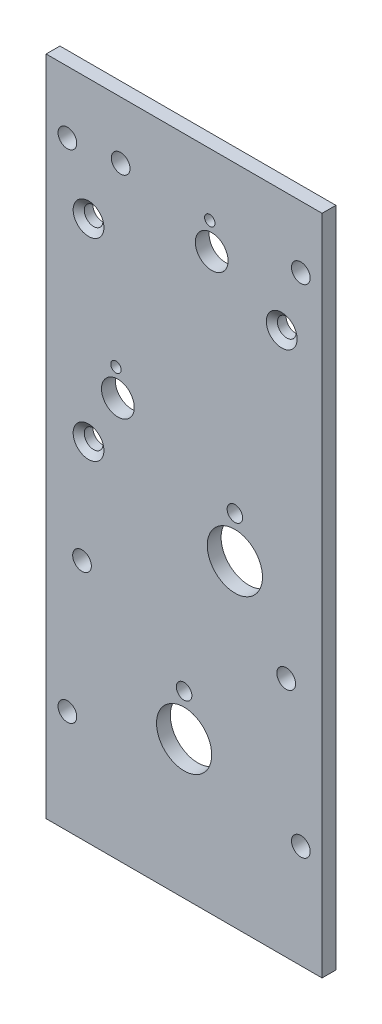
SolidWorks part; units mm, degrees
material "Acrylic (Medium-high impact)"
ref_plane "Front Plane" through (0, 0, 0) normal (0, 0, 1) x (1, 0, 0)
ref_plane "Top Plane" through (0, 0, 0) normal (0, 1, 0) x (1, 0, 0)
ref_plane "Right Plane" through (0, 0, 0) normal (1, 0, 0) x (0, 0, -1)
sketch "Sketch1" plane through (0, 0, 0) normal (0, 0, 1) x (1, 0, 0)
  line L8 (31.75, -152.4) -> (31.75, 0)
  line L9 (31.75, 0) -> (-31.75, 0)
  line L10 (-31.75, 0) -> (-31.75, -152.4)
  line L11 (-31.75, -152.4) -> (31.75, -152.4)
extrude "Boss-Extrude1" add sketch "Sketch1" against normal blind 3.175
hole_wizard "#6 Clearance Hole1" positions "Sketch3" profile "Sketch2" hole size "#6" standard "ANSI Inch" end condition up to next
sketch "Sketch3" plane through (0, 0, 0) normal (0, 0, 1) x (1, 0, 0)
  point P0 (-26.8605, -14.2875)
  point P2 (26.8605, -14.2875)
  point P4 (26.8605, -128.5875)
  point P6 (-26.8605, -128.5875)
sketch "Sketch2" plane through (-26.8605, -14.2875, 0) normal (1, 0, 0) x (0, -1, 0)
  line L0 (0, 0) -> (0, 3.175)
  line L1 (0, 3.175) -> (2.1526, 3.175)
  line L2 (2.1526, 3.175) -> (2.1526, 0)
  line L5 (2.1526, 0) -> (0, 0)
  line L11 (0, -6.35) -> (0, 107.95) construction
  dimension "Thru Hole Dia." = 4.3053
  dimension "Thru Hole Depth" = 3.175
hole_wizard "#6 Clearance Hole2" positions "Sketch5" profile "Sketch4" hole size "#6" standard "ANSI Inch" end condition up to next
sketch "Sketch5" plane through (0, 0, 0) normal (0, 0, 1) x (1, 0, 0)
  point P0 (-23.495, -96.8375)
  point P2 (23.495, -96.8375)
  point P4 (-14.605, -13.208)
sketch "Sketch4" plane through (-23.495, -96.8375, 0) normal (1, 0, 0) x (0, -1, 0)
  line L0 (0, 0) -> (0, 3.175)
  line L1 (0, 3.175) -> (2.1526, 3.175)
  line L2 (2.1526, 3.175) -> (2.1526, 0)
  line L5 (2.1526, 0) -> (0, 0)
  line L11 (0, -6.35) -> (0, 107.95) construction
  dimension "Thru Hole Dia." = 4.3053
  dimension "Thru Hole Depth" = 3.175
hole_wizard "1/2 (0.5) Diameter Hole1" positions "Sketch7" profile "Sketch6" hole size "1/2" standard "ANSI Inch" end condition up to next
sketch "Sketch7" plane through (0, 0, 0) normal (0, 0, 1) x (1, 0, 0)
  point P4 (11.684, -79.375)
  point P6 (0, -120.65)
sketch "Sketch6" plane through (11.684, -79.375, 0) normal (1, 0, 0) x (0, -1, 0)
  line L0 (0, 0) -> (0, 3.175)
  line L1 (0, 3.175) -> (6.35, 3.175)
  line L2 (6.35, 3.175) -> (6.35, 0)
  line L5 (6.35, 0) -> (0, 0)
  line L11 (0, -6.35) -> (0, 107.95) construction
  dimension "Thru Hole Dia." = 12.7
  dimension "Thru Hole Depth" = 3.175
hole_wizard "9/64 (0.14063) Diameter Hole1" positions "Sketch9" profile "Sketch8" hole size "9/64" standard "ANSI Inch" end condition up to next
sketch "Sketch9" plane through (0, 0, 0) normal (0, 0, 1) x (1, 0, 0)
  point P0 (0, -111.125)
  point P2 (11.684, -69.85)
sketch "Sketch8" plane through (0, -111.125, 0) normal (1, 0, 0) x (0, -1, 0)
  line L0 (0, 0) -> (0, 3.175)
  line L1 (0, 3.175) -> (1.786, 3.175)
  line L2 (1.786, 3.175) -> (1.786, 0)
  line L5 (1.786, 0) -> (0, 0)
  line L11 (0, -6.35) -> (0, 107.95) construction
  dimension "Thru Hole Dia." = 3.572
  dimension "Thru Hole Depth" = 3.175
hole_wizard "19/64 (0.29688) Diameter Hole1" positions "Sketch11" profile "Sketch10" hole size "19/64" standard "ANSI Inch" end condition up to next
sketch "Sketch11" plane through (0, 0, 0) normal (0, 0, 1) x (1, 0, 0)
  point P0 (-15.24, -60.325)
  point P2 (6.35, -20.32)
sketch "Sketch10" plane through (-15.24, -60.325, 0) normal (1, 0, 0) x (0, -1, 0)
  line L0 (0, 0) -> (0, 3.175)
  line L1 (0, 3.175) -> (3.7704, 3.175)
  line L2 (3.7704, 3.175) -> (3.7704, 0)
  line L5 (3.7704, 0) -> (0, 0)
  line L11 (0, -6.35) -> (0, 107.95) construction
  dimension "Thru Hole Dia." = 7.5408
  dimension "Thru Hole Depth" = 3.175
hole_wizard "CSK for #6 Flat Head Machine Screw (100)1" positions "Sketch12" profile "Sketch13" countersink size "#6" standard "ANSI Inch" end condition up to next
sketch "Sketch12" plane through (0, 0, 0) normal (0, 0, 1) x (1, 0, 0)
  circle A0 centre (-21.99, -72.39) radius 2.15 construction
  circle A1 centre (-21.99, -27.94) radius 2.15 construction
  circle A2 centre (22.46, -27.94) radius 2.15 construction
  point P0 (-21.99, -72.39)
  point P5 (-21.99, -27.94)
  point P7 (22.46, -27.94)
sketch "Sketch13" plane through (-21.99, -72.39, 0) normal (1, 0, 0) x (0, -1, 0)
  line L0 (0, 0) -> (0, 3.175)
  line L1 (0, 3.175) -> (2.1526, 3.175)
  line L2 (2.1526, 3.175) -> (2.1526, 1.1669)
  line L3 (2.1526, 1.1669) -> (3.5433, 0)
  line L5 (3.5433, 0) -> (0, 0)
  line L6 (-2.1526, 1.1669) -> (-3.5433, 0) construction
  line L11 (0, -6.35) -> (0, 107.95) construction
  dimension "Thru Hole Dia." = 4.3053
  dimension "Thru Hole Depth" = 3.175
  dimension "Near C'Sink Dia." = 7.0866
  dimension "Near C'Sink Angle" = 100
hole_wizard "3/32 (0.09375) Diameter Hole1" positions "Sketch14" profile "Sketch15" hole size "3/32" standard "ANSI Inch" end condition up to next
sketch "Sketch14" plane through (0, 0, 0) normal (0, 0, 1) x (1, 0, 0)
  line L0 (-11.9489, -54.0615) -> (-19.4279, -54.622) construction
  line L1 (9.6411, -14.0565) -> (2.1621, -14.617) construction
  point P0 (-15.6884, -54.3418)
  point P4 (5.9016, -14.3368)
sketch "Sketch15" plane through (-15.6884, -54.3418, 0) normal (1, 0, 0) x (0, -1, 0)
  line L0 (0, 0) -> (0, 3.175)
  line L1 (0, 3.175) -> (1.1906, 3.175)
  line L2 (1.1906, 3.175) -> (1.1906, 0)
  line L5 (1.1906, 0) -> (0, 0)
  line L11 (0, -6.35) -> (0, 107.95) construction
  dimension "Thru Hole Dia." = 2.3812
  dimension "Thru Hole Depth" = 3.175
